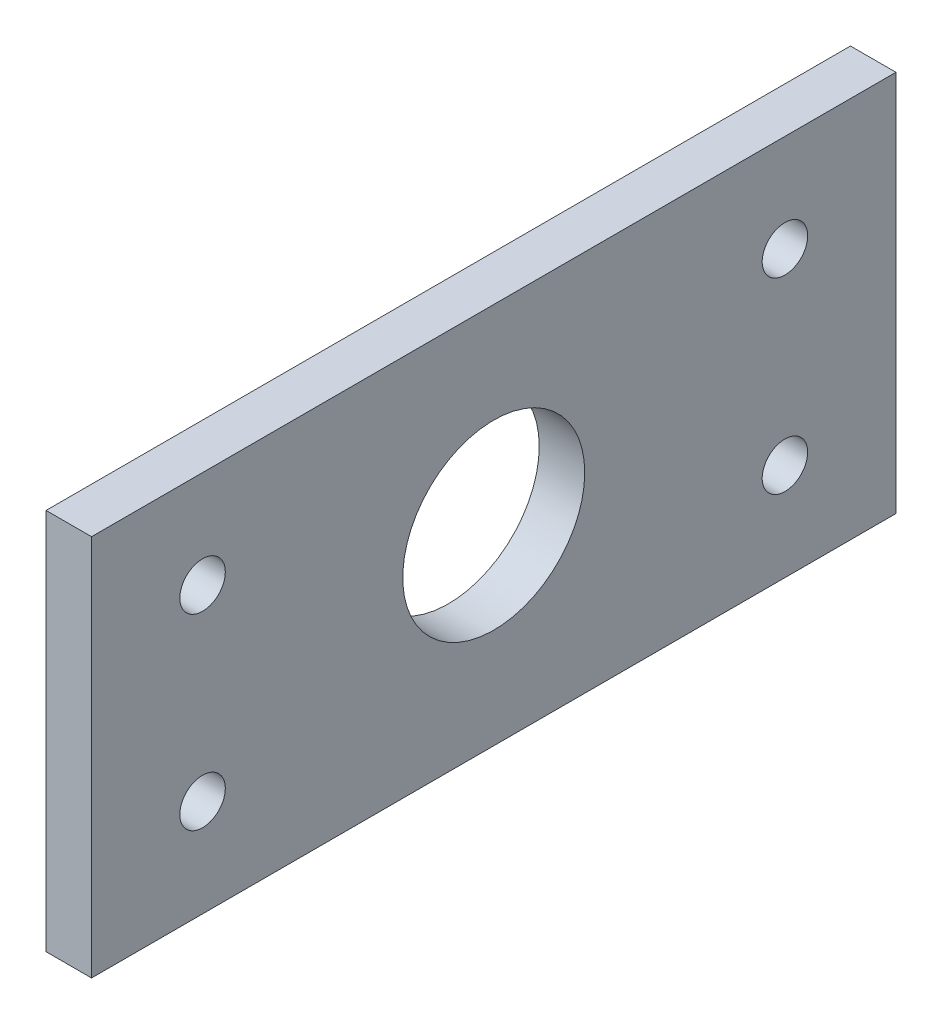
SolidWorks part; units mm, degrees
ref_plane "Front Plane" through (0, 0, 0) normal (0, 0, 1) x (1, 0, 0)
ref_plane "Top Plane" through (0, 0, 0) normal (0, 1, 0) x (1, 0, 0)
ref_plane "Right Plane" through (0, 0, 0) normal (1, 0, 0) x (0, 0, -1)
sketch "Sketch1" plane through (0, 0, 0) normal (1, 0, 0) x (0, 0, -1)
  line L1 (-56.134, -26.67) -> (56.134, -26.67)
  line L2 (-56.134, -26.67) -> (-56.134, 26.67)
  line L3 (-56.134, 26.67) -> (56.134, 26.67)
  line L4 (56.134, -26.67) -> (56.134, 26.67)
  line L5 (-56.134, -26.67) -> (56.134, 26.67) construction
  line L6 (-56.134, 26.67) -> (56.134, -26.67) construction
  circle A0 centre (0, 0) radius 12.7
  circle A1 centre (-40.64, -13.081) radius 3.175
  circle A2 centre (40.64, -13.081) radius 3.175
  circle A3 centre (-40.64, 13.081) radius 3.175
  circle A4 centre (40.64, 13.081) radius 3.175
  point P0 (0, 0)
  dimension "D3" = 25.4
  dimension "D4" = 6.35
  dimension "D5" = 6.35
  dimension "D6" = 13.589
  dimension "D7" = 15.494
  dimension "D8" = 13.589
  dimension "D9" = 15.494
  dimension "D10" = 13.589
  dimension "D11" = 13.589
  dimension "D12" = 15.494
  dimension "D13" = 15.494
  dimension "D1" = 112.268
  dimension "D2" = 53.34
extrude "Boss-Extrude1" add sketch "Sketch1" along normal blind 6.35
